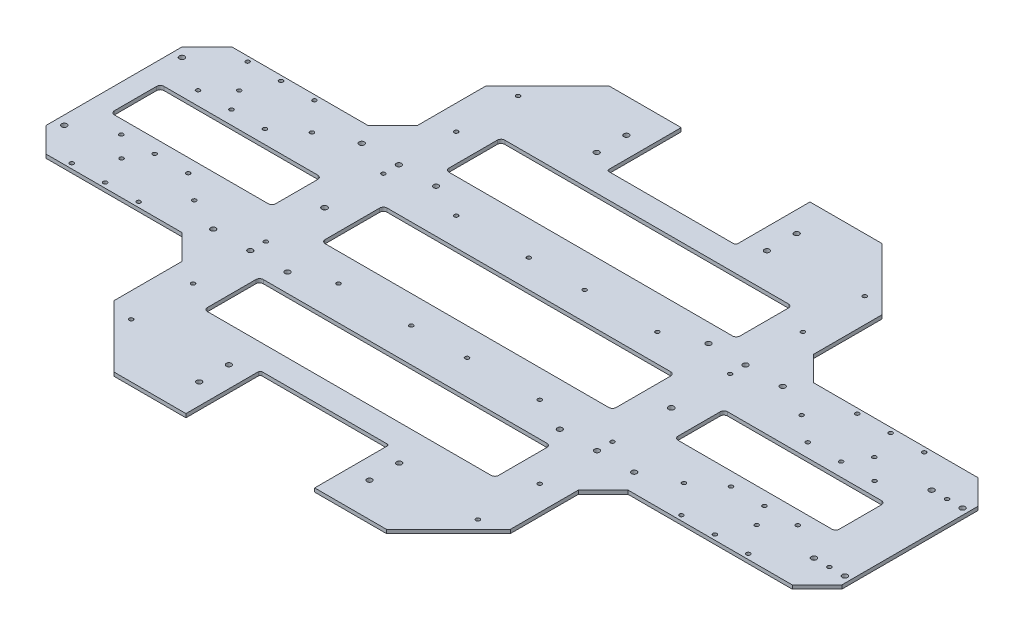
SolidWorks part; units mm, degrees
material "6061-O (SS)"
ref_plane "前视基准面" through (0, 0, 0) normal (0, 0, 1) x (1, 0, 0)
ref_plane "上视基准面" through (0, 0, 0) normal (0, 1, 0) x (1, 0, 0)
ref_plane "右视基准面" through (0, 0, 0) normal (1, 0, 0) x (0, 0, -1)
sketch "草图1" plane through (0, 0, 0) normal (0, 1, 0) x (1, 0, 0)
  line L0 (0, 0) -> (160, -38.7097) construction
  line L1 (-260, 200) -> (260, 200) construction
  line L2 (-260, 200) -> (-260, -200) construction
  line L3 (-260, -200) -> (260, -200) construction
  line L4 (260, 200) -> (260, -200) construction
  line L5 (-260, 200) -> (-160, 123.0769) construction
  line L6 (-260, -200) -> (-160, -123.0769) construction
  line L7 (-310, -75) -> (-160, -75)
  line L8 (-310, -75) -> (-310, 75)
  line L9 (-310, 75) -> (-160, 75)
  line L10 (310, -75) -> (310, 75)
  line L11 (-310, -75) -> (160, 38.7097) construction
  line L12 (-310, 75) -> (-160, 38.7097) construction
  line L13 (-160, -200) -> (160, -200)
  line L14 (-160, -200) -> (-160, -75)
  line L15 (-160, 200) -> (160, 200)
  line L16 (160, -200) -> (160, -75)
  line L17 (-60, -75) -> (0, 0) construction
  line L18 (0, 0) -> (60, -75) construction
  line L19 (-160, 75) -> (-160, 200)
  line L22 (160, 75) -> (310, 75)
  line L24 (97.5, 75) -> (260, 200) construction
  line L25 (160, 75) -> (160, 200)
  line L26 (260, 62.9032) -> (310, 75) construction
  line L27 (260, -62.9032) -> (310, -75) construction
  line L28 (160, -75) -> (310, -75)
  line L29 (160, -123.0769) -> (260, -200) construction
  point P0 (0, 0)
  point P6 (0, 0)
  point P11 (0, 0)
  dimension "D1" = 520
  dimension "D2" = 400
  dimension "D3" = 50
  dimension "D4" = 125
  dimension "D5" = 100
extrude "凸台-拉伸1" add sketch "草图1" along normal blind 3
chamfer "倒角1" distance 20 angle 45 8 edges at (-160, 1.5, -75) (-310, 1.5, -75) (-310, 1.5, 75) (-160, 1.5, 75) (160, 1.5, 75) (160, 1.5, -75) (310, 1.5, 75) (310, 1.5, -75)
chamfer "倒角2" distance 50 angle 45 4 edges at (160, 1.5, 200) (-160, 1.5, 200) (160, 1.5, -200) (-160, 1.5, -200)
sketch "草图2" plane through (0, 0, 0) normal (0, -1, 0) x (-1, 0, 0)
  line L1 (52, -140) -> (-52, -140)
  line L2 (52, -140) -> (52, -233.0888)
  line L3 (52, -233.0888) -> (-52, -233.0888)
  line L4 (-52, -140) -> (-52, -233.0888)
  line L6 (0, 0) -> (119.8246, 0) construction
  line L7 (-52, 140) -> (-52, 233.0888)
  line L8 (52, 233.0888) -> (-52, 233.0888)
  line L9 (52, 140) -> (52, 233.0888)
  line L10 (52, 140) -> (-52, 140)
  line L11 (160, -95) -> (160, -150) construction
  line L12 (-160, -150) -> (-160, -95) construction
  dimension "D1" = 108
  dimension "D2" = 108
extrude "切除-拉伸1" cut sketch "草图2" against normal blind 40
fillet "圆角1" radius 1.5 4 edges at (-52, 1.5, -140) (52, 1.5, -140) (52, 1.5, 140) (-52, 1.5, 140)
sketch "草图3" plane through (0, 0, 0) normal (0, -1, 0) x (1, 0, 0)
  circle A0 centre (-68.75, 172.5) radius 2.1
  circle A1 centre (-68.75, 148.5) radius 2.1
  circle A2 centre (68.75, 172.5) radius 2.1
  circle A3 centre (68.75, 148.5) radius 2.1
  circle A4 centre (-68.75, -148.5) radius 2.1
  circle A5 centre (-68.75, -172.5) radius 2.1
  circle A6 centre (68.75, -148.5) radius 2.1
  circle A7 centre (68.75, -172.5) radius 2.1
extrude "切除-拉伸2" cut sketch "草图3" against normal blind 80
sketch "草图4" plane through (0, 0, 0) normal (0, -1, 0) x (1, 0, 0)
  line L0 (0, 0) -> (124.2092, 0) construction
  line L1 (0, 0) -> (0, 63.2758) construction
  circle A0 centre (273.2002, 71) radius 1.6
  circle A1 centre (273.2002, 30.9984) radius 1.6
  circle A2 centre (246.2002, 71) radius 1.6
  circle A3 centre (219.2002, 71) radius 1.6
  circle A4 centre (246.2002, 30.9984) radius 1.6
  circle A5 centre (219.2002, 30.9984) radius 1.6
  circle A6 centre (110, 60) radius 2.1
  circle A7 centre (140, 60) radius 2.1
  circle A8 centre (170, 60) radius 2.1
  circle A9 centre (170, -60) radius 2.1
  circle A10 centre (140, -60) radius 2.1
  circle A11 centre (110, -60) radius 2.1
  circle A12 centre (219.2002, -30.9984) radius 1.6
  circle A13 centre (246.2002, -30.9984) radius 1.6
  circle A14 centre (219.2002, -71) radius 1.6
  circle A15 centre (246.2002, -71) radius 1.6
  circle A16 centre (273.2002, -30.9984) radius 1.6
  circle A17 centre (273.2002, -71) radius 1.6
  circle A18 centre (-273.2002, -71) radius 1.6
  circle A19 centre (-273.2002, -30.9984) radius 1.6
  circle A20 centre (-246.2002, -71) radius 1.6
  circle A21 centre (-219.2002, -71) radius 1.6
  circle A22 centre (-246.2002, -30.9984) radius 1.6
  circle A23 centre (-219.2002, -30.9984) radius 1.6
  circle A24 centre (-110, -60) radius 2.1
  circle A25 centre (-140, -60) radius 2.1
  circle A26 centre (-170, -60) radius 2.1
  circle A27 centre (-170, 60) radius 2.1
  circle A28 centre (-140, 60) radius 2.1
  circle A29 centre (-110, 60) radius 2.1
  circle A30 centre (-219.2002, 30.9984) radius 1.6
  circle A31 centre (-246.2002, 30.9984) radius 1.6
  circle A32 centre (-219.2002, 71) radius 1.6
  circle A33 centre (-246.2002, 71) radius 1.6
  circle A34 centre (-273.2002, 30.9984) radius 1.6
  circle A35 centre (-273.2002, 71) radius 1.6
extrude "切除-拉伸3" cut sketch "草图4" against normal blind 29
sketch "草图5" plane through (0, 0, 0) normal (0, -1, 0) x (1, 0, 0)
  line L0 (310, 55) -> (290, 75) construction
  line L1 (310, 55) -> (310, -55) construction
  line L2 (290, -75) -> (310, -55) construction
  line L3 (310, 55) -> (290, 75)
  line L4 (310, 55) -> (310, -55)
  line L5 (290, -75) -> (310, -55)
  line L6 (290, -75) -> (312.7002, -75)
  line L7 (312.7002, -75) -> (332.7002, -55)
  line L9 (332.7002, -55) -> (332.7002, 55)
  line L10 (332.7002, 55) -> (312.7002, 75)
  line L11 (312.7002, 75) -> (290, 75)
extrude "凸台-拉伸2" add sketch "草图5" against normal blind 3
sketch "草图6" plane through (0, 0, 0) normal (0, -1, 0) x (1, 0, 0)
  circle A0 centre (302.7002, 47.5) radius 2.15
  circle A1 centre (327.7002, 47.5) radius 2.15
  circle A2 centre (327.7002, -47.5) radius 2.15
  circle A3 centre (302.7002, -47.5) radius 2.15
  dimension "D1" = 4.3
extrude "切除-拉伸4" cut sketch "草图6" against normal blind 3
sketch "草图7" plane through (0, 0, 0) normal (0, -1, 0) x (1, 0, 0)
  line L0 (180, 75) -> (312.7002, 75) construction
  line L1 (289.7002, -20) -> (165.5, -20)
  line L2 (292.7002, -17) -> (292.7002, 17)
  line L3 (289.7002, 20) -> (165.5, 20)
  line L4 (162.5, -17) -> (162.5, 17)
  line L5 (114.5, -25) -> (-114.5, -25)
  line L6 (117.5, -22) -> (117.5, 22)
  line L7 (114.5, 25) -> (-114.5, 25)
  line L8 (-117.5, -22) -> (-117.5, 22)
  line L9 (114.5, -120) -> (-114.5, -120)
  line L10 (117.5, -117) -> (117.5, -78)
  line L11 (114.5, -75) -> (-114.5, -75)
  line L12 (-117.5, -117) -> (-117.5, -78)
  line L13 (312.7002, -75) -> (180, -75) construction
  line L14 (307.7002, -40) -> (307.7002, 40) construction
  line L15 (147.5, -40) -> (147.5, 40) construction
  line L16 (-132.5, -40) -> (-132.5, 40) construction
  line L17 (132.5, 40) -> (-132.5, 40) construction
  line L18 (132.5, -40) -> (132.5, 40) construction
  line L19 (132.5, -40) -> (-132.5, -40) construction
  line L20 (132.5, -55) -> (-132.5, -55) construction
  line L21 (132.5, -55) -> (132.5, -279) construction
  line L22 (-132.5, -55) -> (-132.5, -279) construction
  line L23 (45.4531, 0) -> (0, 0) construction
  line L24 (0, 0) -> (0, 77.4247) construction
  line L25 (-162.5, -17) -> (-162.5, 17)
  line L26 (-289.7002, 20) -> (-165.5, 20)
  line L27 (-292.7002, -17) -> (-292.7002, 17)
  line L28 (-289.7002, -20) -> (-165.5, -20)
  line L29 (-117.5, 117) -> (-117.5, 78)
  line L30 (114.5, 75) -> (-114.5, 75)
  line L31 (117.5, 117) -> (117.5, 78)
  line L32 (114.5, 120) -> (-114.5, 120)
  arc A0 (289.7002, -20) -> (292.7002, -17) centre (289.7002, -17) ccw
  arc A1 (292.7002, 17) -> (289.7002, 20) centre (289.7002, 17) ccw
  arc A2 (165.5, -20) -> (162.5, -17) centre (165.5, -17) cw
  arc A3 (165.5, 20) -> (162.5, 17) centre (165.5, 17) ccw
  arc A4 (114.5, -120) -> (117.5, -117) centre (114.5, -117) ccw
  arc A5 (-114.5, -120) -> (-117.5, -117) centre (-114.5, -117) cw
  arc A6 (-114.5, -75) -> (-117.5, -78) centre (-114.5, -78) ccw
  arc A7 (117.5, -78) -> (114.5, -75) centre (114.5, -78) ccw
  arc A8 (114.5, -25) -> (117.5, -22) centre (114.5, -22) ccw
  arc A9 (117.5, 22) -> (114.5, 25) centre (114.5, 22) ccw
  arc A10 (-114.5, -25) -> (-117.5, -22) centre (-114.5, -22) cw
  arc A11 (-114.5, 25) -> (-117.5, 22) centre (-114.5, 22) ccw
  arc A12 (-165.5, 20) -> (-162.5, 17) centre (-165.5, 17) cw
  arc A13 (-165.5, -20) -> (-162.5, -17) centre (-165.5, -17) ccw
  arc A14 (-292.7002, 17) -> (-289.7002, 20) centre (-289.7002, 17) cw
  arc A15 (-289.7002, -20) -> (-292.7002, -17) centre (-289.7002, -17) cw
  arc A16 (117.5, 78) -> (114.5, 75) centre (114.5, 78) cw
  arc A17 (-114.5, 75) -> (-117.5, 78) centre (-114.5, 78) cw
  arc A18 (-114.5, 120) -> (-117.5, 117) centre (-114.5, 117) ccw
  arc A19 (114.5, 120) -> (117.5, 117) centre (114.5, 117) cw
  point P46 (-117.5, -120)
  point P49 (-117.5, -75)
  dimension "D13" = 3
  dimension "D1" = 55
  dimension "D2" = 55
  dimension "D3" = 15
  dimension "D4" = 15
  dimension "D5" = 15
  dimension "D6" = 15
  dimension "D7" = 15
  dimension "D8" = 15
  dimension "D9" = 20
  dimension "D10" = 15
  dimension "D11" = 15
  dimension "D12" = 45
extrude "切除-拉伸5" cut sketch "草图7" against normal blind 15
sketch "草图8" plane through (0, 0, 0) normal (0, -1, 0) x (1, 0, 0)
  line L0 (40.5777, 0) -> (-40.5777, 0) construction
  line L1 (0, 0) -> (0, 30.149) construction
  circle A0 centre (140, 0) radius 2.2407 construction
  circle A1 centre (140, 156.23) radius 1.6 construction
  circle A2 centre (140, 106.23) radius 1.6 construction
  circle A3 centre (22.54, 47.5) radius 1.6 construction
  circle A4 centre (81.27, 47.5) radius 1.6 construction
  circle A5 centre (140, 47.5) radius 1.6 construction
  circle A6 centre (197.7368, 47.5) radius 1.6 construction
  circle A7 centre (256.4668, 47.5) radius 1.6 construction
  circle A8 centre (315.2002, 47.5) radius 1.6 construction
  circle A9 centre (140, 0) radius 2.2407
  circle A10 centre (140, 156.23) radius 1.6
  circle A11 centre (140, 106.23) radius 1.6
  circle A12 centre (22.54, 47.5) radius 1.6
  circle A13 centre (81.27, 47.5) radius 1.6
  circle A14 centre (140, 47.5) radius 1.6
  circle A15 centre (197.7368, 47.5) radius 1.6
  circle A16 centre (256.4668, 47.5) radius 1.6
  circle A17 centre (315.2002, 47.5) radius 1.6
  circle A18 centre (315.2002, -47.5) radius 1.6
  circle A19 centre (256.4668, -47.5) radius 1.6
  circle A20 centre (197.7368, -47.5) radius 1.6
  circle A21 centre (140, -47.5) radius 1.6
  circle A22 centre (81.27, -47.5) radius 1.6
  circle A23 centre (22.54, -47.5) radius 1.6
  circle A24 centre (140, -106.23) radius 1.6
  circle A25 centre (140, -156.23) radius 1.6
  circle A26 centre (-140, -156.23) radius 1.6
  circle A27 centre (-140, -106.23) radius 1.6
  circle A28 centre (-22.54, -47.5) radius 1.6
  circle A29 centre (-81.27, -47.5) radius 1.6
  circle A30 centre (-140, -47.5) radius 1.6
  circle A31 centre (-197.7368, -47.5) radius 1.6
  circle A32 centre (-256.4668, -47.5) radius 1.6
  circle A33 centre (-315.2002, -47.5) radius 1.6
  circle A34 centre (-315.2002, 47.5) radius 1.6
  circle A35 centre (-256.4668, 47.5) radius 1.6
  circle A36 centre (-197.7368, 47.5) radius 1.6
  circle A37 centre (-140, 47.5) radius 1.6
  circle A38 centre (-81.27, 47.5) radius 1.6
  circle A39 centre (-22.54, 47.5) radius 1.6
  circle A40 centre (-140, 106.23) radius 1.6
  circle A41 centre (-140, 156.23) radius 1.6
  circle A42 centre (-140, 0) radius 2.2407
  circle A43 centre (-302.7002, -47.5) radius 2.15 construction
  circle A44 centre (-302.7002, 47.5) radius 2.15 construction
  circle A45 centre (-302.7002, -47.5) radius 2.15
  circle A46 centre (-302.7002, 47.5) radius 2.15
extrude "切除-拉伸6" cut sketch "草图8" against normal blind 15
